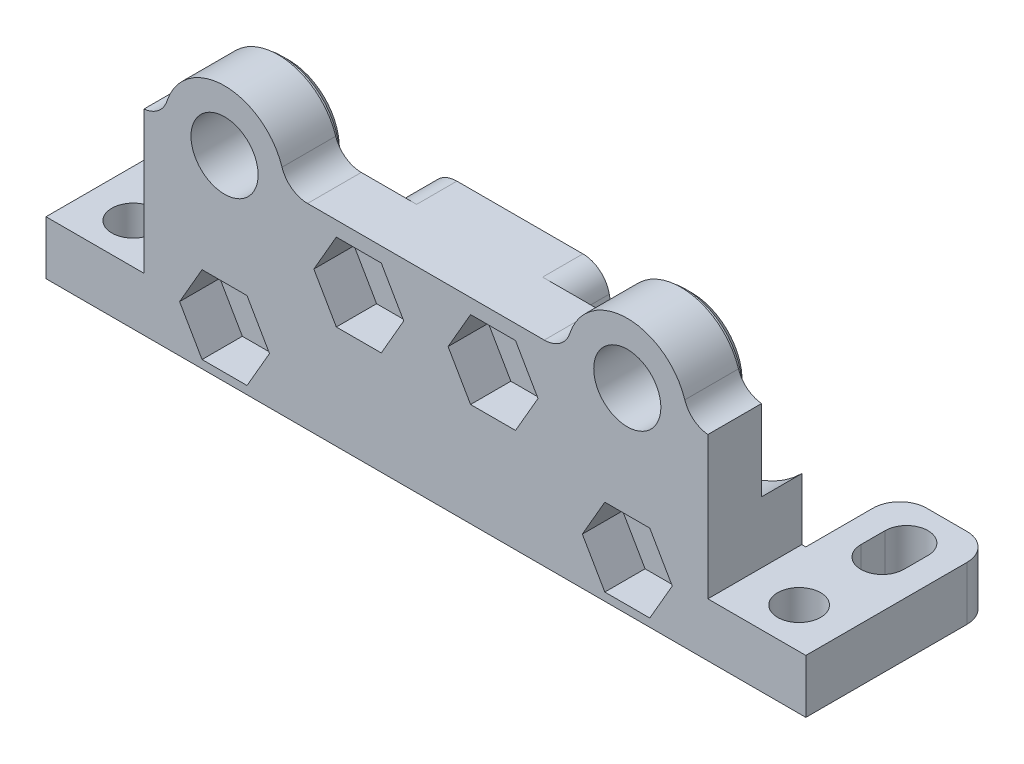
SolidWorks part; units mm, degrees
ref_plane "Front Plane" through (0, 0, 0) normal (0, 0, 1) x (1, 0, 0)
ref_plane "Top Plane" through (0, 0, 0) normal (0, 1, 0) x (1, 0, 0)
ref_plane "Right Plane" through (0, 0, 0) normal (1, 0, 0) x (0, 0, -1)
sketch "Sketch1" plane through (0, 0, 0) normal (0, 0, 1) x (1, 0, 0)
  line L0 (0, 0) -> (0, -69.5054) construction
  line L1 (-9, -41.3642) -> (9, -41.3642)
  line L2 (-21, -41.3642) -> (-21, -55.9642)
  line L3 (-21, -55.9642) -> (21, -55.9642)
  line L4 (21, -55.9642) -> (21, -41.3642)
  circle A0 centre (0, 0) radius 37 construction
  circle A1 centre (15, -41.3642) radius 7 construction
  circle A2 centre (15, -41.3642) radius 2.5
  circle A3 centre (15, -41.3642) radius 6
  circle A4 centre (-15, -41.3642) radius 2.5
  circle A5 centre (-15, -41.3642) radius 6
  dimension "D1" = 74
  dimension "D2" = 14
  dimension "D4" = 5
  dimension "D5" = 12
  dimension "D3" = 30
  dimension "D6" = 14.6
extrude "Boss-Extrude1" add sketch "Sketch1" along normal blind 4 contours L1 A5 L2 L3 L4 A3 | A5 A4 | A3 A2 region at (-15, -47.1945, 0) region at (0, -49.7392, 0) region at (15, -35.5339, 0)
sketch "Sketch2" plane through (0, 0, 0) normal (0, 0, -1) x (-1, 0, 0)
  circle A0 centre (15, -41.3642) radius 2.5 construction
  circle A1 centre (-15, -41.3642) radius 2.5 construction
  circle A2 centre (15, -41.3642) radius 2.5
  circle A3 centre (-15, -41.3642) radius 2.5
  circle A4 centre (-15, -41.3642) radius 4.25
  circle A5 centre (15, -41.3642) radius 4.25
  dimension "D1" = 8.5
extrude "Boss-Extrude2" add sketch "Sketch2" along normal blind 0.8
sketch "Sketch3" plane through (0, 0, 0) normal (0, 0, -1) x (-1, 0, 0)
  line L4 (4.6922, -41.3642) -> (-4.6922, -41.3642)
  line L5 (21, -55.9642) -> (21, -47.385)
  line L6 (-21, -55.9642) -> (21, -55.9642)
  line L7 (-21, -47.385) -> (-21, -55.9642)
  line L8 (4.6922, -41.3642) -> (-4.6922, -41.3642)
  line L9 (21, -55.9642) -> (21, -47.385)
  line L10 (-21, -55.9642) -> (21, -55.9642)
  line L11 (-21, -47.385) -> (-21, -55.9642)
  arc A2 (-21, -47.385) -> (-6.6556, -42.9833) centre (-15, -41.3642) ccw
  arc A3 (6.6556, -42.9833) -> (21, -47.385) centre (15, -41.3642) ccw
  arc A4 (-21, -47.385) -> (-6.6556, -42.9833) centre (-15, -41.3642) ccw
  arc A5 (6.6556, -42.9833) -> (21, -47.385) centre (15, -41.3642) ccw
  arc A26 (-4.6922, -41.3642) -> (-6.6556, -42.9833) centre (-4.6922, -43.3642) ccw
  arc A27 (-4.6922, -41.3642) -> (-6.6556, -42.9833) centre (-4.6922, -43.3642) ccw
  arc A28 (6.6556, -42.9833) -> (4.6922, -41.3642) centre (4.6922, -43.3642) ccw
  arc A29 (6.6556, -42.9833) -> (4.6922, -41.3642) centre (4.6922, -43.3642) ccw
  dimension "D1" = 0
extrude "Boss-Extrude3" add sketch "Sketch3" along normal blind 3
sketch "Sketch4" plane through (0, 0, 4) normal (0, 0, 1) x (1, 0, 0)
  circle A0 centre (-15, -52.4642) radius 1.6 construction
  circle A1 centre (-5, -45.3642) radius 1.6 construction
  circle A2 centre (5, -45.3642) radius 1.6 construction
  circle A3 centre (15, -52.4642) radius 1.6 construction
  circle A4 centre (-15, -52.4642) radius 1.6
  circle A5 centre (-5, -45.3642) radius 1.6
  circle A6 centre (5, -45.3642) radius 1.6
  circle A7 centre (15, -52.4642) radius 1.6
extrude "Cut-Extrude1" cut sketch "Sketch4" against normal through all
sketch "Sketch5" plane through (0, -55.9642, 0) normal (0, -1, 0) x (1, 0, 0)
  line L0 (-21, 4) -> (-28.3, 4)
  line L1 (-28.3, 4) -> (-28.3, -10)
  line L2 (-28.3, -10) -> (-21.3, -10)
  line L3 (-21.3, -10) -> (-21.3, -3)
  line L4 (-21.3, -3) -> (-21, -3)
  line L5 (-21, -3) -> (-21, 4)
  line L6 (-21, -10.6) -> (-21, -3.1) construction
  line L7 (0, 0) -> (0, 4) construction
  line L8 (-21, 4) -> (21, 4) construction
  line L9 (-24.8, -10) -> (-24.8, 4) construction
  line L10 (-24.8, -5.2) -> (-24.8, -7) construction
  line L11 (-23.2, -5.2) -> (-23.2, -7)
  line L12 (-26.4, -5.2) -> (-26.4, -7)
  line L13 (24.8, -5.2) -> (24.8, -7) construction
  line L14 (23.2, -5.2) -> (23.2, -7)
  line L15 (26.4, -5.2) -> (26.4, -7)
  line L16 (24.8, -10) -> (24.8, 4) construction
  line L17 (21, -3) -> (21, 4)
  line L18 (21.3, -3) -> (21, -3)
  line L19 (21.3, -10) -> (21.3, -3)
  line L20 (28.3, -10) -> (21.3, -10)
  line L21 (28.3, 4) -> (28.3, -10)
  line L22 (21, 4) -> (28.3, 4)
  circle A0 centre (-24.8, 1) radius 1.6
  arc A1 (-23.2, -5.2) -> (-26.4, -5.2) centre (-24.8, -5.2) ccw
  arc A2 (-26.4, -7) -> (-23.2, -7) centre (-24.8, -7) ccw
  arc A3 (23.2, -5.2) -> (26.4, -5.2) centre (24.8, -5.2) cw
  arc A4 (26.4, -7) -> (23.2, -7) centre (24.8, -7) cw
  circle A5 centre (24.8, 1) radius 1.6
  point P21 (-24.8, -6.1)
  point P28 (24.8, -6.1)
  dimension "D4" = 3.2
  dimension "D7" = 5
  dimension "D1" = 0.3
  dimension "D2" = 7
  dimension "D3" = 14
  dimension "D5" = 3
  dimension "D6" = 3
extrude "Boss-Extrude4" add sketch "Sketch5" against normal blind 4
sketch "Sketch6" plane through (0, 0, 4) normal (0, 0, 1) x (1, 0, 0)
  line L0 (-10.5, -41.3642) -> (-9, -41.3642)
  line L1 (9, -41.3642) -> (10.5, -41.3642)
  line L2 (-19.5, -41.3642) -> (-21, -41.3642)
  line L3 (19.5, -41.3642) -> (21, -41.3642)
  arc A0 (-9, -41.3642) -> (-21, -41.3642) centre (-15, -41.3642) ccw construction
  arc A1 (-9, -41.3642) -> (-21, -41.3642) centre (-15, -41.3642) ccw
  arc A2 (21, -41.3642) -> (9, -41.3642) centre (15, -41.3642) ccw construction
  arc A3 (21, -41.3642) -> (9, -41.3642) centre (15, -41.3642) ccw
  arc A4 (-10.5, -41.3642) -> (-19.5, -41.3642) centre (-15, -41.3642) ccw
  arc A5 (19.5, -41.3642) -> (10.5, -41.3642) centre (15, -41.3642) ccw
  dimension "D1" = 1.5
  dimension "D2" = 1.5
extrude "Cut-Extrude2" cut sketch "Sketch6" against normal blind 4
sketch "Sketch7" plane through (0, 0, 4) normal (0, 0, 1) x (1, 0, 0)
  line L1 (-8.3486, -45.3642) -> (-6.6743, -48.2642)
  line L2 (-6.6743, -48.2642) -> (-3.3257, -48.2642)
  line L3 (-3.3257, -48.2642) -> (-1.6514, -45.3642)
  line L4 (-1.6514, -45.3642) -> (-3.3257, -42.4642)
  line L5 (-3.3257, -42.4642) -> (-6.6743, -42.4642)
  line L6 (-6.6743, -42.4642) -> (-8.3486, -45.3642)
  line L7 (1.6514, -45.3642) -> (3.3257, -48.2642)
  line L8 (3.3257, -48.2642) -> (6.6743, -48.2642)
  line L9 (6.6743, -48.2642) -> (8.3486, -45.3642)
  line L10 (8.3486, -45.3642) -> (6.6743, -42.4642)
  line L11 (6.6743, -42.4642) -> (3.3257, -42.4642)
  line L12 (3.3257, -42.4642) -> (1.6514, -45.3642)
  line L13 (-11.6514, -52.4642) -> (-13.3257, -49.5642)
  line L14 (-13.3257, -49.5642) -> (-16.6743, -49.5642)
  line L15 (-16.6743, -49.5642) -> (-18.3486, -52.4642)
  line L16 (-18.3486, -52.4642) -> (-16.6743, -55.3642)
  line L17 (-16.6743, -55.3642) -> (-13.3257, -55.3642)
  line L18 (-13.3257, -55.3642) -> (-11.6514, -52.4642)
  line L19 (11.6514, -52.4642) -> (13.3257, -55.3642)
  line L20 (13.3257, -55.3642) -> (16.6743, -55.3642)
  line L21 (16.6743, -55.3642) -> (18.3486, -52.4642)
  line L22 (18.3486, -52.4642) -> (16.6743, -49.5642)
  line L23 (16.6743, -49.5642) -> (13.3257, -49.5642)
  line L24 (13.3257, -49.5642) -> (11.6514, -52.4642)
  circle A0 centre (-5, -45.3642) radius 2.9 construction
  circle A1 centre (5, -45.3642) radius 2.9 construction
  circle A2 centre (-15, -52.4642) radius 2.9 construction
  circle A3 centre (15, -52.4642) radius 2.9 construction
  dimension "D1" = 5.8
extrude "Cut-Extrude3" cut sketch "Sketch7" against normal blind 3
sketch "Sketch8" plane through (0, 0, 1) normal (0, 0, 1) x (1, 0, 0)
  circle A0 centre (15, -52.4642) radius 1.6 construction
  circle A1 centre (5, -45.3642) radius 1.6 construction
  circle A2 centre (-5, -45.3642) radius 1.6 construction
  circle A3 centre (-15, -52.4642) radius 1.6 construction
  circle A4 centre (15, -52.4642) radius 1.6
  circle A5 centre (5, -45.3642) radius 1.6
  circle A6 centre (-5, -45.3642) radius 1.6
  circle A7 centre (-15, -52.4642) radius 1.6
extrude "Boss-Extrude5" add sketch "Sketch8" against normal blind 0.4
fillet "Fillet1" radius 2 8 edges at (-10.5, -41.3642, 2) (10.5, -41.3642, 2) (-19.5, -41.3642, 2) (19.5, -41.3642, 2) (28.3, -53.9642, -10) (21.3, -53.9642, -10) (-21.3, -53.9642, -10) (-28.3, -53.9642, -10)
chamfer "Chamfer1" distance 0.5 angle 45 2 edges at (10.75, -41.3642, -0.8) (-19.25, -41.3642, -0.8)
